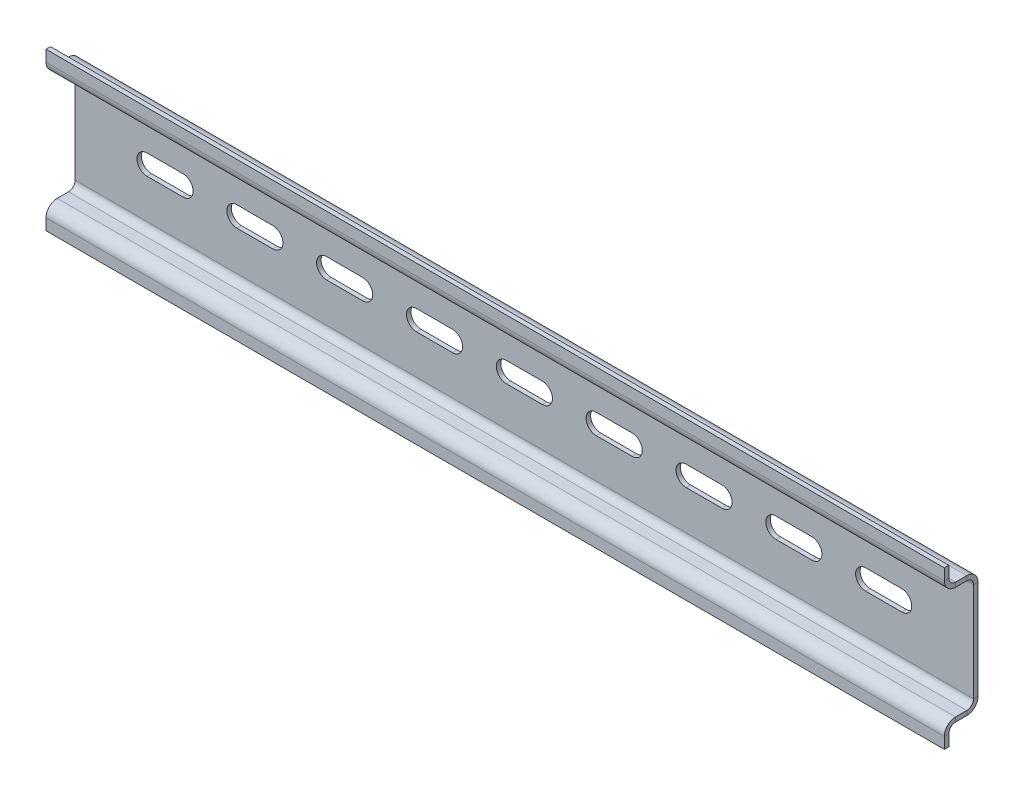
SolidWorks part; units mm, degrees
note: The reader was unsure of these and kept them because the rebuilt part matched: flange length of "边线-法兰1", "边线-法兰2".
ref_plane "前视基准面" through (0, 0, 0) normal (0, 0, 1) x (1, 0, 0)
ref_plane "上视基准面" through (0, 0, 0) normal (0, 1, 0) x (1, 0, 0)
ref_plane "右视基准面" through (0, 0, 0) normal (1, 0, 0) x (0, 0, -1)
sketch "草图1" plane through (0, 0, 0) normal (0, 0, 1) x (1, 0, 0)
  line L1 (-100, 13.5) -> (100, 13.5)
  line L2 (-100, 13.5) -> (-100, -13.5)
  line L3 (-100, -13.5) -> (100, -13.5)
  line L4 (100, 13.5) -> (100, -13.5)
  line L5 (-100, 13.5) -> (100, -13.5) construction
  line L6 (-100, -13.5) -> (100, 13.5) construction
  point P0 (0, 0)
  dimension "D1" = 200
  dimension "D2" = 27
base flange "基体-法兰1" sketch "草图1" thickness 1 reverse thickness direction no parameters "D1"=1.5
edge flange "边线-法兰1" sketch "草图10" flange profiles "草图10", "草图11" flange angle 90 flange length 7.5 flange position material inside bend radius 1.5 thickness 1 relief obround parameters "D1"=2, "D6"=10, "D8"=1
sketch "草图10" plane through (0, 13.5, 0) normal (0, -1, 0) x (1, 0, 0)
  line L1 (100, 0) -> (-100, 0) construction
  line L2 (-100, 0) -> (-100, 6.5)
  line L3 (-100, 6.5) -> (100, 6.5)
  line L4 (100, 6.5) -> (100, 0)
  line L5 (100, 0) -> (-100, 0)
sketch "草图11" plane through (0, -13.5, 0) normal (0, 1, 0) x (-1, 0, 0)
  line L0 (100, 0) -> (-100, 0) construction
  line L1 (100, 0) -> (-100, 0)
  line L2 (100, 0) -> (100, 6.5)
  line L3 (100, 6.5) -> (-100, 6.5)
  line L4 (-100, 6.5) -> (-100, 0)
bend "边线折弯1" bend radius 1.5 bend angle 90 parameters "D5"=1
bend "边线折弯2" bend radius 1.5 bend angle 90 parameters "D5"=2
edge flange "边线-法兰2" sketch "草图16" flange profiles "草图16", "草图17" flange angle 90 flange length 5 flange position material inside bend radius 1.5 thickness 1 relief obround parameters "D1"=2, "D6"=10, "D8"=1
sketch "草图16" plane through (0, 13.5, 6.5) normal (0, 0, 1) x (1, 0, 0)
  line L2 (-100, 0) -> (-100, 4)
  line L3 (-100, 4) -> (100, 4)
  line L4 (100, 4) -> (100, 0)
  line L5 (100, 0) -> (-100, 0) construction
  line L6 (100, 0) -> (-100, 0)
sketch "草图17" plane through (0, -13.5, 6.5) normal (0, 0, 1) x (-1, 0, 0)
  line L0 (100, 0) -> (-100, 0) construction
  line L1 (100, 0) -> (-100, 0)
  line L2 (-100, 0) -> (-100, 4)
  line L3 (-100, 4) -> (100, 4)
  line L4 (100, 4) -> (100, 0)
bend "边线折弯3" bend radius 1.5 bend angle 90 parameters "D5"=3
bend "边线折弯4" bend radius 1.5 bend angle 90 parameters "D5"=4
sketch "草图18" plane through (0, 0, -1) normal (0, 0, -1) x (-1, 0, 0)
  line L0 (-4, 0) -> (4, 0) construction
  line L1 (-4, 2.25) -> (4, 2.25)
  line L2 (-4, -2.25) -> (4, -2.25)
  arc A0 (-4, 2.25) -> (-4, -2.25) centre (-4, 0) ccw
  arc A1 (4, -2.25) -> (4, 2.25) centre (4, 0) ccw
  point P3 (0, 0)
  dimension "D2" = 2.25
  dimension "D1" = 8
  dimension "D3" = 0
extrude "切除-拉伸1" cut sketch "草图18" against normal blind 10 normal cut yes
pattern_linear "阵列(线性)1" count 5 spacing 20 along (1, 0, 0) count 5 spacing 20 along (-1, 0, 0) of "切除-拉伸1"
sketch "折弯-线1" plane through (0, 0, 0) normal (0, 1, 0) x (1, 0, 0)
sketch "边界框1" plane through (0, 0, 0) normal (0, 1, 0) x (1, 0, 0)
sheet metal parameters "钣金9" thickness 1 parameters "D1"=1
flat pattern "平板型式9" [suppressed]
sketch "折弯-线2" plane through (0, 0, 0) normal (0, 1, 0) x (1, 0, 0)
sketch "边界框2" [suppressed] plane through (0, 0, 0) normal (0, 1, 0) x (1, 0, 0)
sheet metal parameters "钣金10" thickness 1 parameters "D1"=1
flat pattern "平板型式9" [suppressed]
sketch "折弯-线2" plane through (0, 0, 0) normal (0, 1, 0) x (1, 0, 0)
sketch "边界框2" [suppressed] plane through (0, 0, 0) normal (0, 1, 0) x (1, 0, 0)
bend of the flat pattern "展开-<边线折弯1>1"
bend of the flat pattern "展开-<边线折弯2>1"
sheet metal parameters "钣金11" thickness 1 parameters "D1"=1
flat pattern "平板型式9" [suppressed]
sketch "折弯-线2" plane through (0, 0, 0) normal (0, 1, 0) x (1, 0, 0)
sketch "边界框2" [suppressed] plane through (0, 0, 0) normal (0, 1, 0) x (1, 0, 0)
bend of the flat pattern "展开-<边线折弯1>1"
bend of the flat pattern "展开-<边线折弯2>1"
bend of the flat pattern "展开-<边线折弯3>1"
bend of the flat pattern "展开-<边线折弯4>1"
sheet metal parameters "钣金12" thickness 1 parameters "D1"=1
flat pattern "平板型式9" [suppressed]
sketch "折弯-线2" plane through (0, 0, 0) normal (0, 1, 0) x (1, 0, 0)
sketch "边界框2" [suppressed] plane through (0, 0, 0) normal (0, 1, 0) x (1, 0, 0)
bend of the flat pattern "展开-<边线折弯1>1"
bend of the flat pattern "展开-<边线折弯2>1"
bend of the flat pattern "展开-<边线折弯3>1"
bend of the flat pattern "展开-<边线折弯4>1"
sheet metal parameters "钣金13" thickness 1 parameters "D1"=1
flat pattern "平板型式9" [suppressed]
sketch "折弯-线2" plane through (0, 0, 0) normal (0, 1, 0) x (1, 0, 0)
sketch "边界框2" [suppressed] plane through (0, 0, 0) normal (0, 1, 0) x (1, 0, 0)
bend of the flat pattern "展开-<边线折弯1>1"
bend of the flat pattern "展开-<边线折弯2>1"
bend of the flat pattern "展开-<边线折弯3>1"
bend of the flat pattern "展开-<边线折弯4>1"
